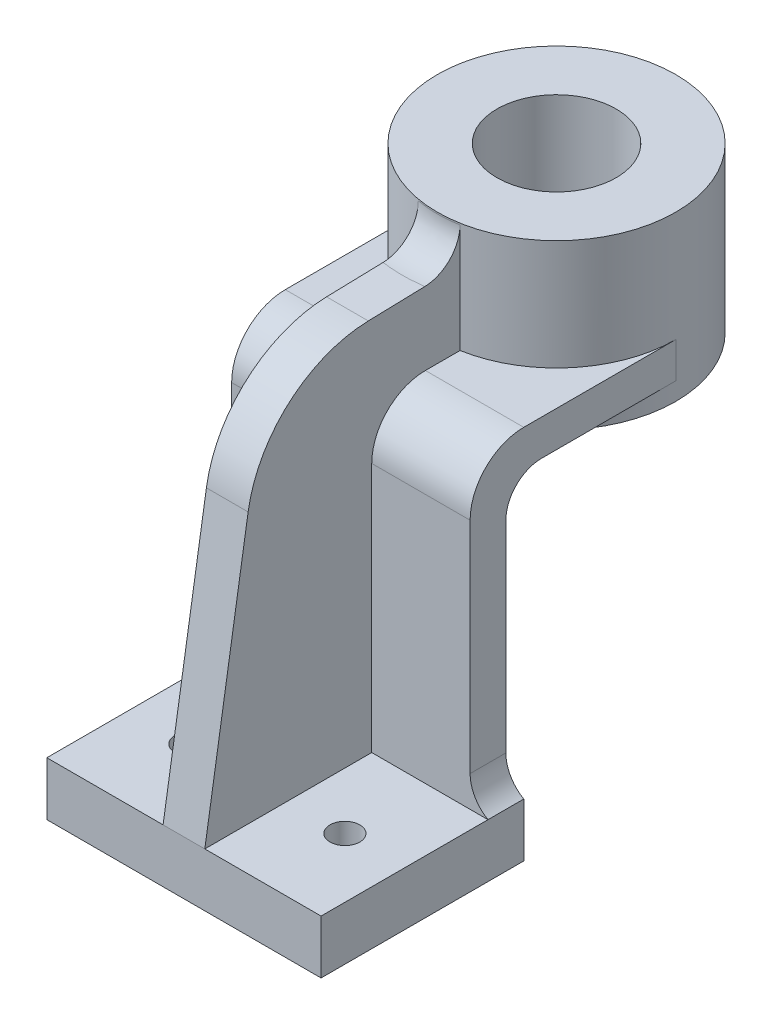
SolidWorks part; units mm, degrees
ref_plane "Front Plane" through (0, 0, 0) normal (0, 0, 1) x (1, 0, 0)
ref_plane "Top Plane" through (0, 0, 0) normal (0, 1, 0) x (1, 0, 0)
ref_plane "Right Plane" through (0, 0, 0) normal (1, 0, 0) x (0, 0, -1)
sketch "Sketch1" plane through (0, 0, 0) normal (1, 0, 0) x (0, 0, -1)
  line L1 (-34, 9) -> (34, 9)
  line L2 (-34, 9) -> (-34, -9)
  line L3 (-34, -9) -> (34, -9)
  line L4 (34, 9) -> (34, -9)
  line L5 (-34, 9) -> (34, -9) construction
  line L6 (-34, -9) -> (34, 9) construction
  point P0 (0, 0)
  dimension "D1" = 68
  dimension "D2" = 18
extrude "Boss-Extrude1" add sketch "Sketch1" along normal mid plane 92
sketch "Sketch2" plane through (0, 0, 0) normal (1, 0, 0) x (0, 0, -1)
  line L0 (34, 9) -> (22, 9)
  line L1 (34, 9) -> (-34, 9) construction
  line L2 (22, 9) -> (22, 111)
  line L3 (22, 111) -> (91, 111)
  line L4 (91, 111) -> (91, 99)
  line L5 (91, 99) -> (34, 99)
  line L6 (34, 99) -> (34, 9)
  line L7 (-34, 9) -> (-34, -9) construction
  dimension "D1" = 12
  dimension "D2" = 12
  dimension "D3" = 102
  dimension "D4" = 125
extrude "Boss-Extrude2" add sketch "Sketch2" along normal mid plane 80
fillet "Fillet1" radius 12 2 edges at (-40, 9, -28) (40, 9, -28)
fillet "Fillet3" radius 18 1 edges at (0, 111, -22)
fillet "Fillet4" radius 12 1 edges at (0, 99, -34)
sketch "Sketch3" plane through (0, 111, 0) normal (0, 1, 0) x (1, 0, 0)
  line L0 (40, 91) -> (-40, 91) construction
  circle A0 centre (0, 91) radius 40
  dimension "D1" = 80
extrude "Boss-Extrude3" add sketch "Sketch3" along normal blind 37 and the other way blind 18
hole_wizard "Hole1" positions "Sketch4" profile "Sketch5" legacy end condition through all
sketch "Sketch4" plane through (0, 148, 0) normal (0, 1, 0) x (1, 0, 0)
  point P0 (0, 91)
sketch "Sketch5" plane through (0, 148, -91) normal (1, 0, 0) x (0, 0, 1)
  line L0 (0, 0) -> (0, 157)
  line L1 (0, 157) -> (20, 157)
  line L2 (20, 157) -> (20, 0)
  line L3 (20, 0) -> (0, 0)
  line L4 (0, 110) -> (0, -10) construction
  dimension "Diameter" = 40
  dimension "Depth" = 157
sketch "Sketch6" plane through (0, 0, 0) normal (1, 0, 0) x (0, 0, -1)
  line L0 (-34, 9) -> (-19.4707, 99.6471)
  line L1 (20.85, 134.9843) -> (57.9321, 136)
  line L3 (22, 9) -> (-34, 9) construction
  line L4 (22, 19.3923) -> (22, 9) construction
  line L5 (22, 93) -> (22, 19.3923) construction
  line L6 (91, 111) -> (40, 111) construction
  line L7 (22, 9) -> (-34, 9)
  line L8 (22, 19.3923) -> (22, 9)
  line L9 (22, 93) -> (22, 19.3923)
  line L10 (57.9321, 111) -> (40, 111)
  line L11 (57.9321, 136) -> (57.9321, 111)
  line L12 (51, 93) -> (131, 93) construction
  line L13 (131, 93) -> (131, 148) construction
  arc A0 (-19.4707, 99.6471) -> (20.85, 134.9843) centre (22, 93) cw
  arc A1 (40, 111) -> (22, 93) centre (40, 93) ccw construction
  arc A2 (40, 111) -> (22, 93) centre (40, 93) ccw
  point P2 (0, 111)
  point P14 (0, 0)
  point P17 (0, 0)
  point P18 (0, 0)
  point P19 (-34, 9)
  point P20 (-319.9992, 170.8523)
  dimension "D1" = 42
  dimension "D2" = 43
  dimension "D3" = 73.0679
extrude "Boss-Extrude5" add sketch "Sketch6" along normal mid plane 14
fillet "Fillet5" radius 12 1 edges at (0, 135.8101, -51)
hole_wizard "Hole2" positions "Sketch7" profile "Sketch8" legacy end condition through all
sketch "Sketch7" plane through (0, 9, 0) normal (0, 1, 0) x (1, 0, 0)
  line L0 (46, 22) -> (46, -34) construction
  line L1 (46, -34) -> (7, -34) construction
  point P0 (26, -6)
  point P5 (0, 0)
  dimension "D1" = 20
  dimension "D2" = 28
sketch "Sketch8" plane through (26, 9, 6) normal (1, 0, 0) x (0, 0, 1)
  line L0 (0, 0) -> (0, 18)
  line L1 (0, 18) -> (5, 18)
  line L2 (5, 18) -> (5, 0)
  line L3 (5, 0) -> (0, 0)
  line L4 (0, 110) -> (0, -10) construction
  dimension "Diameter" = 10
  dimension "Depth" = 18
mirror "Mirror1" about plane through (0, 0, 0) normal (1, 0, 0) of "Hole2"
